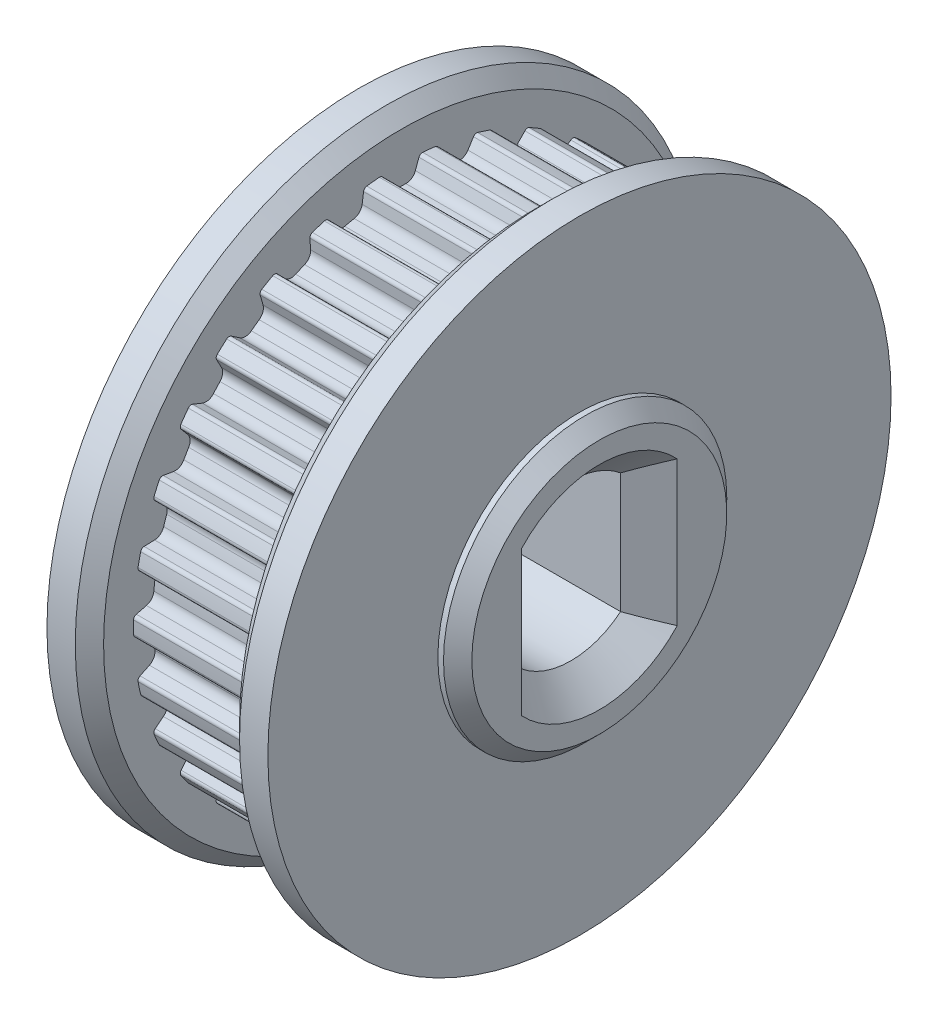
SolidWorks part; units mm, degrees
ref_plane "前视基准面" through (0, 0, 0) normal (0, 0, 1) x (1, 0, 0)
ref_plane "上视基准面" through (0, 0, 0) normal (0, 1, 0) x (1, 0, 0)
ref_plane "右视基准面" through (0, 0, 0) normal (1, 0, 0) x (0, 0, -1)
sketch "草图1" plane through (0, 0, 0) normal (0, 0, 1) x (1, 0, 0)
  line L0 (0, 0) -> (64.8368, 0) construction
  line L1 (0, 1.75) -> (0, 9.446)
  line L2 (0, 9.446) -> (4.8, 9.446)
  line L3 (4.8, 9.446) -> (4.8, 5)
  line L4 (4.8, 5) -> (7, 5)
  line L5 (7, 5) -> (7, 1.75)
  line L6 (7, 1.75) -> (0, 1.75)
  dimension "L" = 7
  dimension "B" = 4.8
  dimension "d" = 3.5
  dimension "d1" = 10
  dimension "da" = 18.892
revolve "旋转1" add sketch "草图1" angle 360 about L0
sketch "草图7" plane through (0, 0, 0) normal (-1, 0, 0) x (0, 0, 1)
  circle A1 centre (0, 0) radius 1.75 construction
  circle A2 centre (0, 0) radius 11
  circle A3 centre (0, 0) radius 1.75
  dimension "D1" = 22
extrude "凸台-拉伸1" add sketch "草图7" along normal blind 1.5
sketch "草图8" plane through (7, 0, 0) normal (1, 0, 0) x (0, 0, -1)
  line L2 (-1.75, 2.1213) -> (-1.75, -2.1213)
  line L4 (1.75, 2.1213) -> (1.75, -2.1213)
  arc A0 (-1.75, -2.1213) -> (1.75, -2.1213) centre (0, 0) ccw
  arc A1 (1.75, 2.1213) -> (-1.75, 2.1213) centre (0, 0) ccw
  dimension "D1" = 3.5
  dimension "D2" = 5.5
extrude "切除-拉伸3" cut sketch "草图8" against normal through all
chamfer "倒角1" distance 1 angle 45 8 edges at (-1.5, -2.75, 0) (-1.5, 0, 1.75) (-1.5, 0, -1.75) (-1.5, 2.75, 0) (7, -2.75, 0) (7, 0, -1.75) (7, 2.75, 0) (7, 0, 1.75)
ref_axis "基准轴1" through (-0.35, 0, 0) along (1, 0, 0)
sketch "草图6" plane through (0, 0, 0) normal (1, 0, 0) x (0, 0, -1)
  line L0 (0, 0) -> (0, 16.0158) construction
  line L1 (0.6325, 9.3298) -> (0.5069, 8.9846)
  line L2 (0.8947, 9.4035) -> (1.3928, 10.772)
  line L3 (-0.8947, 9.4035) -> (-1.3928, 10.772)
  line L4 (-0.6325, 9.3298) -> (-0.5069, 8.9846)
  circle A0 centre (0, 0) radius 9.446 construction
  arc A1 (0.1711, 8.7543) -> (-0.1711, 8.7543) centre (0, 0) ccw
  arc A2 (0.7652, 9.415) -> (0.8947, 9.4035) centre (0, 0) cw
  arc A3 (0.5069, 8.9846) -> (0.1711, 8.7543) centre (0.178, 9.1043) cw
  arc A4 (0.6325, 9.3298) -> (0.7652, 9.415) centre (0.7547, 9.2854) cw
  arc A5 (1.3928, 10.772) -> (-1.3928, 10.772) centre (0, 0) ccw
  arc A6 (-0.7652, 9.415) -> (-0.8947, 9.4035) centre (0, 0) ccw
  arc A7 (-0.6325, 9.3298) -> (-0.7652, 9.415) centre (-0.7547, 9.2854) ccw
  arc A8 (-0.5069, 8.9846) -> (-0.1711, 8.7543) centre (-0.178, 9.1043) ccw
  point P8 (0, 15.3258)
  point P14 (0.6662, 9.4225)
  point P16 (0.42, 8.7459)
  dimension "D1" = 8.756
  dimension "ra" = 0.13
  dimension "rf" = 0.35
  dimension "D3" = 1.4563
  dimension "D4" = 0.13
  dimension "bw" = 0.84
  dimension "angle" = 40
  dimension "hg" = 0.69
extrude "切除-拉伸2" cut sketch "草图6" along normal up to next
pattern_circular "阵列(圆周)3" count 30 over 360 about axis through (-0.35, 0, 0) along (1, 0, 0) of "切除-拉伸2"
chamfer "倒角2" distance 0.5 angle 45 2 edges at (0, 0, 11) (7, 0, 5)
sketch "草图9" plane through (4.8, 0, 0) normal (1, 0, 0) x (0, 0, -1)
  circle A0 centre (0, 0) radius 5 construction
  circle A1 centre (0, 0) radius 11 construction
  circle A2 centre (0, 0) radius 5
  circle A3 centre (0, 0) radius 11
extrude "凸台-拉伸2" add sketch "草图9" along normal blind 1.5 separate body
chamfer "倒角3" distance 0.5 angle 45 2 edges at (4.8, 0, -5) (4.8, 0, -11)
equation "\"D4@草图6\" = \"ra@草图6\""
equation "\"D1@草图6\" = \"da@草图1\" / 2 - \"hg@草图6\" "
